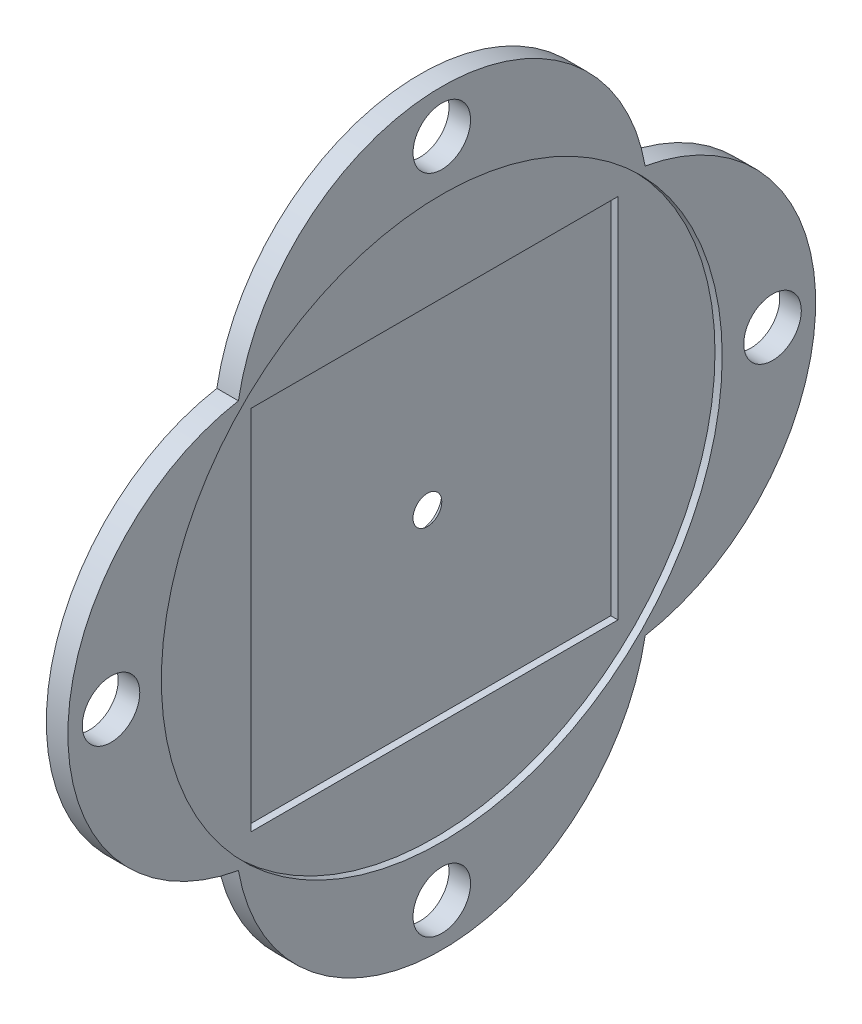
SolidWorks part; units mm, degrees
ref_plane "Front Plane" through (0, 0, 0) normal (0, 0, 1) x (1, 0, 0)
ref_plane "Top Plane" through (0, 0, 0) normal (0, 1, 0) x (1, 0, 0)
ref_plane "Right Plane" through (0, 0, 0) normal (1, 0, 0) x (0, 0, -1)
sketch "Sketch2" plane through (0, 0, 0) normal (1, 0, 0) x (0, 0, -1)
  line L1 (-14.1421, -14.1421) -> (14.1421, -14.1421) construction
  line L2 (-14.1421, -14.1421) -> (-14.1421, 14.1421) construction
  line L3 (-14.1421, 14.1421) -> (14.1421, 14.1421) construction
  line L4 (14.1421, -14.1421) -> (14.1421, 14.1421) construction
  circle A1 centre (0, 23) radius 2
  circle A2 centre (23, 0) radius 2
  circle A3 centre (0, -23) radius 2
  circle A4 centre (-23, 0) radius 2
  circle A5 centre (0, 0) radius 7.5 construction
  circle A6 centre (0, 0) radius 8.5 construction
  circle A10 centre (0, 0) radius 18 construction
  circle A11 centre (0, 0) radius 26 construction
  circle A12 centre (0, -23) radius 3 construction
  circle A14 centre (23, 0) radius 3 construction
  arc A25 (-14.1421, 14.1421) -> (-14.1421, -14.1421) centre (-11.6378, 0) ccw
  arc A26 (-14.1421, -14.1421) -> (14.1421, -14.1421) centre (0, -11.6378) ccw
  circle A27 centre (0, 0) radius 20 construction
  arc A28 (14.1421, 14.1421) -> (-14.1421, 14.1421) centre (0, 11.6378) ccw
  arc A29 (14.1421, -14.1421) -> (14.1421, 14.1421) centre (11.6378, 0) ccw
  point P14 (0, 0)
  point P36 (0, 0)
  point P49 (0, 0)
  dimension "D1" = 36
  dimension "D3" = 4
  dimension "D5" = 15
  dimension "D6" = 17
  dimension "D7" = 52
  dimension "D8" = 40
  dimension "D4" = 23
  dimension "D2" = 4
  dimension "D9" = 4
extrude "Body" add sketch "Sketch2" along normal mid plane 1.5
sketch "Sketch3" plane through (0.75, 0, 0) normal (1, 0, 0) x (0, 0, -1)
  circle A0 centre (0, 0) radius 19.5
  dimension "D1" = 39
extrude "O-Ring Seat" cut sketch "Sketch3" against normal blind 0.5
sketch "Sketch11" plane through (0.25, 0, 0) normal (1, 0, 0) x (0, 0, -1)
  line L1 (-12.75, 12.75) -> (12.75, 12.75)
  line L2 (-12.75, 12.75) -> (-12.75, -12.75)
  line L3 (-12.75, -12.75) -> (12.75, -12.75)
  line L4 (12.75, 12.75) -> (12.75, -12.75)
  circle A0 centre (0, 0) radius 18.0312 construction
  dimension "D1" = 25.5
extrude "Mesh Recess" cut sketch "Sketch11" against normal blind 0.5
sketch "Sketch12" plane through (-0.25, 0, 0) normal (1, 0, 0) x (0, 0, -1)
  circle A0 centre (0, 0) radius 0.5
  dimension "D1" = 1
extrude "Cut-Extrude4" cut sketch "Sketch12" against normal through all
chamfer "Chamfer1" distance 1 angle 45 1 edges at (-0.75, 0, -0.5)
